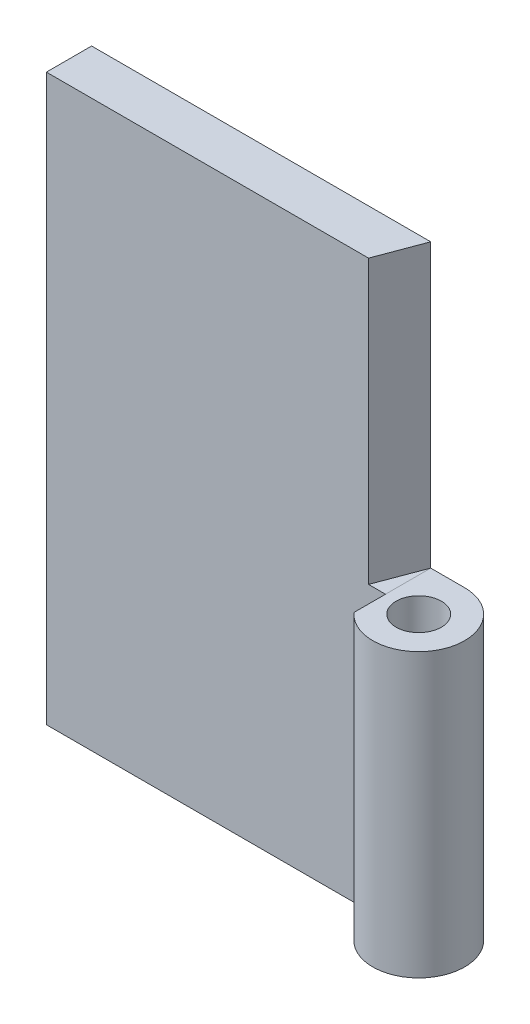
SolidWorks part; units mm, degrees
ref_plane "Front Plane" through (0, 0, 0) normal (0, 0, 1) x (1, 0, 0)
ref_plane "Top Plane" through (0, 0, 0) normal (0, 1, 0) x (1, 0, 0)
ref_plane "Right Plane" through (0, 0, 0) normal (1, 0, 0) x (0, 0, -1)
sketch "Sketch1" plane through (0, 0, 0) normal (0, 0, 1) x (1, 0, 0)
  line L1 (0, 0) -> (15, 0)
  line L2 (0, 0) -> (0, -25)
  line L3 (0, -25) -> (15, -25)
  line L4 (15, 0) -> (15, -25)
  dimension "D1" = 15
  dimension "D2" = 25
extrude "Boss-Extrude1" add sketch "Sketch1" along normal blind 2
sketch "Sketch2" plane through (0, 0, 0) normal (0, 1, 0) x (1, 0, 0)
  line L0 (15, 0) -> (16.5, 0)
  line L2 (15, 0) -> (15, -3.4)
  arc A0 (15, -3.4) -> (16.5, 0) centre (16.5, -2.0309) ccw
  dimension "D1" = 3.4
  dimension "D2" = 1.5
sketch "Sketch4" plane through (0, -25, 0) normal (0, -1, 0) x (1, 0, 0)
  line L4 (15, 0) -> (16.5, 0)
  line L5 (15, 3.4) -> (15, 0)
  line L6 (15, 0) -> (16.5, 0)
  line L7 (15, 3.4) -> (15, 0)
  arc A2 (16.5, 0) -> (15, 3.4) centre (16.5, 2.0309) ccw
  arc A3 (16.5, 0) -> (15, 3.4) centre (16.5, 2.0309) ccw
  dimension "D1" = 0
extrude "Boss-Extrude3" add sketch "Sketch4" against normal blind 12.5 separate body
sketch "Sketch5" plane through (0, -25, 0) normal (0, -1, 0) x (1, 0, 0)
  circle A0 centre (16.5, 2.0309) radius 1
  arc A1 (16.5, 0) -> (15, 3.4) centre (16.5, 2.0309) ccw construction
  dimension "D1" = 2
extrude "Cut-Extrude2" cut sketch "Sketch5" against normal through all
sketch "Sketch7" plane through (0, 0, 0) normal (0, 1, 0) x (1, 0, 0)
  line L1 (15, -2) -> (0, -2) construction
  line L3 (15, -2) -> (15, 0) construction
  line L4 (15, 0) -> (14.25, -2)
  line L5 (14.25, -2) -> (15, -2)
  line L6 (15, -2) -> (15, 0)
  dimension "D1" = 0.75
extrude "Cut-Extrude4" cut sketch "Sketch7" against normal up to surface (12.5 mm away) up to face at (16.5, -12.5, 1.0309)
